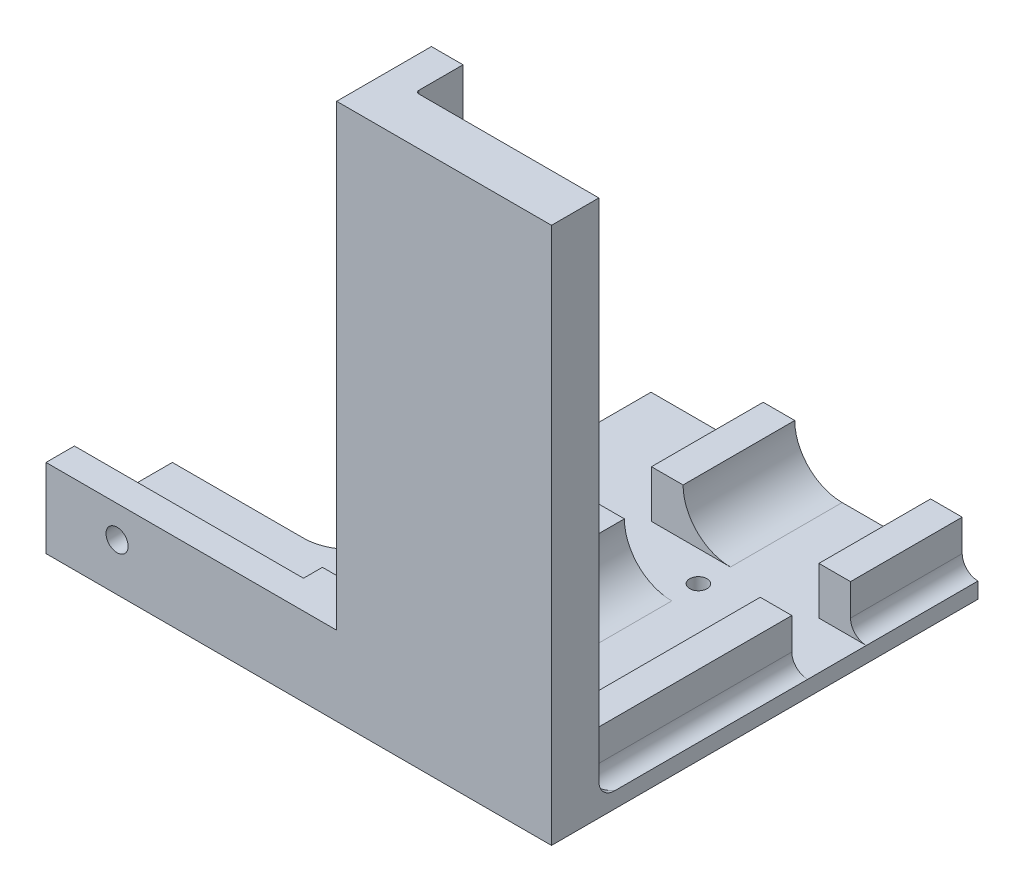
SolidWorks part; units mm, degrees
ref_plane "Front Plane" through (0, 0, 0) normal (0, 0, 1) x (1, 0, 0)
ref_plane "Top Plane" through (0, 0, 0) normal (0, 1, 0) x (1, 0, 0)
ref_plane "Right Plane" through (0, 0, 0) normal (1, 0, 0) x (0, 0, -1)
sketch "profile" plane through (0, 0, 0) normal (0, 0, 1) x (1, 0, 0)
  line L0 (11.8803, 7.4874) -> (14.5, 7.4874)
  line L1 (-5.5, 6.9749) -> (-7.8749, 4.6)
  line L2 (-7.8749, 4.6) -> (-12.1251, 4.6)
  line L3 (-12.1251, 4.6) -> (-14.5, 6.9749)
  line L4 (-8.1197, 7.4874) -> (-5.5, 7.4874)
  line L5 (-14.5, 6.9749) -> (-15.0126, 7.4874)
  line L6 (14.5, 6.9749) -> (12.1251, 4.6)
  line L7 (12.1251, 4.6) -> (7.8749, 4.6)
  line L8 (7.8749, 4.6) -> (5.5, 6.9749)
  line L9 (-14.7464, 10.3536) -> (-5.2536, 10.3536)
  line L10 (-14.5, 7.4874) -> (-11.8803, 7.4874)
  line L11 (5.5, 7.4874) -> (8.5334, 7.4874)
  line L12 (5.6673, 10.3536) -> (14.7464, 10.3536)
  line L13 (-15.0126, 7.4874) -> (-14.5, 7.4874)
  line L14 (-5.5, 6.9749) -> (-4.9874, 7.4874)
  line L15 (-4.9874, 7.4874) -> (-5.5, 7.4874)
  line L16 (5.5, 6.9749) -> (4.9874, 7.4874)
  line L17 (4.9874, 7.4874) -> (5.5, 7.4874)
  line L18 (14.5, 6.9749) -> (15.0126, 7.4874)
  line L19 (15.0126, 7.4874) -> (14.5, 7.4874)
  line L20 (-12.7464, 8.3536) -> (-14.7464, 10.3536)
  line L21 (-5.2536, 10.3536) -> (-7.2536, 8.3536)
  line L22 (7.6673, 8.3536) -> (5.6673, 10.3536)
  line L23 (14.7464, 10.3536) -> (12.7464, 8.3536)
  line L24 (-12.7464, 8.3536) -> (-11.8803, 7.4874)
  line L25 (-7.2536, 8.3536) -> (-8.1197, 7.4874)
  line L26 (7.6673, 8.3536) -> (8.5334, 7.4874)
  line L27 (12.7464, 8.3536) -> (11.8803, 7.4874)
  line L28 (-14.7464, 10.3536) -> (-20, 10.3536)
  line L29 (-20, 10.3536) -> (-20, 15.3536)
  line L30 (-20, 15.3536) -> (20, 15.3536)
  line L31 (20, 15.3536) -> (20, 10.3536)
  line L32 (20, 10.3536) -> (14.7464, 10.3536)
  line L33 (-5.2536, 10.3536) -> (5.6673, 10.3536)
  point P0 (-10, 4.6)
  point P1 (10, 4.6)
  dimension "D1" = 4.2503
  dimension "D2" = 5.7536
  dimension "D3" = 15.7497
  dimension "D4" = 20
  dimension "D5" = 5
extrude "Boss-Extrude1" add sketch "profile" along normal blind 250 contours L9 L33 L12 L32 L31 L30 L29 L28 region at (0, 12.8536, 0)
extrude "Boss-Extrude2" add sketch "Sketch1<3>" along normal blind 50 separate body contours L25 L21 L9 L20 L24 L10 L13 L5 L3 L2 L1 L14 L15 L4 | L27 L23 L12 L22 L26 L11 L17 L16 L8 L7 L6 L18 L19 L0 region at (10.0959, 7.5838, 0) region at (-10, 7.6238, 0)
sketch "Sketch1<3>" plane through (0, 0, 0) normal (0, 0, 1) x (1, 0, 0) same geometry as "profile"
pattern_linear "LPattern1" count 4 spacing 60 along (0, 0, 1) of "Boss-Extrude2"
sketch "Sketch2" plane through (0, 10.3536, 0) normal (0, -1, 0) x (1, 0, 0)
  line L0 (10, 250) -> (10, 0) construction
  line L1 (-20, 250) -> (20, 250) construction
  line L2 (12.1251, 0) -> (7.8749, 0) construction
  line L3 (-10, 230) -> (-10, 0) construction
  line L4 (-7.8749, 230) -> (-12.1251, 230) construction
  line L5 (-7.8749, 0) -> (-12.1251, 0) construction
  line L6 (-7.8749, 180) -> (-7.8749, 170) construction
  line L7 (-7.8749, 180) -> (-12.1251, 180) construction
  circle A0 centre (-10, 175) radius 2.75
  circle A1 centre (10, 175) radius 2.75
  circle A2 centre (-10, 115) radius 2.75
  circle A3 centre (10, 115) radius 2.75
  circle A4 centre (-10, 55) radius 2.75
  circle A5 centre (10, 55) radius 2.75
  point P21 (-7.8749, 175)
  dimension "D1" = 5.5
  dimension "D2" = 3
extrude "Cut-Extrude1" cut sketch "Sketch2" against normal through all
sketch "upper_acrylic_supp" plane through (0, 15.3536, 0) normal (0, 1, 0) x (1, 0, 0)
  line L0 (-20, 0) -> (20, 0) construction
  line L1 (-20, -250) -> (-34.5, -250) construction
  line L2 (-20, -250) -> (-20, 0) construction
  line L3 (-20, 0) -> (-34.5, 0) construction
  line L4 (-34.5, -250) -> (-34.5, 0) construction
  line L6 (-34.5, -250) -> (-24.5, -250)
  line L7 (-34.5, -250) -> (-34.5, -183.9264)
  line L8 (-34.5, -183.9264) -> (-24.5, -183.9264)
  line L9 (-24.5, -250) -> (-24.5, -183.9264)
  line L10 (-34.5, -165.3527) -> (-24.5, -165.3527)
  line L11 (-34.5, -165.3527) -> (-34.5, -123.8775)
  line L12 (-34.5, -123.8775) -> (-24.5, -123.8775)
  line L13 (-24.5, -165.3527) -> (-24.5, -123.8775)
  line L14 (-34.5, -106.5661) -> (-24.5, -106.5661)
  line L15 (-34.5, -106.5661) -> (-34.5, -64.0089)
  line L16 (-34.5, -64.0089) -> (-24.5, -64.0089)
  line L17 (-24.5, -106.5661) -> (-24.5, -64.0089)
  line L18 (-34.5, -45.5583) -> (-24.5, -45.5583)
  line L19 (-34.5, -45.5583) -> (-34.5, 0)
  line L20 (-34.5, 0) -> (-24.5, 0)
  line L21 (-24.5, -45.5583) -> (-24.5, 0)
  line L22 (-20, -250) -> (-40, -250)
  line L23 (-20, -250) -> (-20, 0)
  line L24 (-20, 0) -> (-40, 0)
  line L25 (-40, -250) -> (-40, 0)
  line M21 (-20, 0) -> (-20, -250)
  dimension "D1" = 5.5
  dimension "D2" = 10
  dimension "D3" = 20
extrude "Boss-Extrude3" add sketch "upper_acrylic_supp" against normal blind 5 contours L25 L22 L24 L21 L18 L19 L17 L14 L15 L16 L13 L10 L11 L12 L9 L6 L7 L8 M21 | L14 L17 L16 L15 | L10 L13 L12 L11 | L6 L9 L8 L7 | L18 L21 L20 L19 region at (-29.5, 15.3536, 216.9632) region at (-30.3215, 15.3536, 123.2164) region at (-29.5, 15.3536, 22.7792) region at (-29.5, 15.3536, 144.6151) region at (-29.5, 15.3536, 85.2875)
extrude "Boss-Extrude4" add sketch "upper_acrylic_supp<3>" along normal blind 15 contours L6 L9 L8 L7 | L10 L13 L12 L11 | L14 L17 L16 L15 | L18 L21 L20 L19 region at (-29.5, 15.3536, 216.9632) region at (-29.5, 15.3536, 22.7792) region at (-29.5, 15.3536, 144.6151) region at (-29.5, 15.3536, 85.2875)
sketch "upper_acrylic_supp<3>" plane through (0, 15.3536, 0) normal (0, 1, 0) x (1, 0, 0) same geometry as "upper_acrylic_supp"
fillet "Fillet1" radius 15 4 edges at (-24.5, 15.3536, 22.7792) (-24.5, 15.3536, 85.2875) (-24.5, 15.3536, 144.6151) (-24.5, 15.3536, 216.9632)
sketch "Sketch4" plane through (0, 15.3536, 0) normal (0, 1, 0) x (1, 0, 0)
  line L0 (20, -250) -> (20, 0) construction
  line L1 (-40, -250) -> (20, -250)
  line L2 (-40, -250) -> (-40, -265)
  line L3 (-40, -265) -> (20, -265)
  line L4 (20, -250) -> (20, -265)
  line L5 (-40, 0) -> (20, 0)
  line L6 (-40, 0) -> (-40, 15)
  line L7 (-40, 15) -> (20, 15)
  line L8 (20, 0) -> (20, 15)
  line L10 (-34.5, -265) -> (-34.5, 15) construction
  dimension "D1" = 15
  dimension "D2" = 15
extrude "Boss-Extrude5" add sketch "Sketch4" along normal mid plane 10
extrude "Boss-Extrude6" add sketch "Sketch4<3>" along normal blind 60
sketch "Sketch4<3>" plane through (0, 15.3536, 0) normal (0, 1, 0) x (1, 0, 0) same geometry as "Sketch4"
sketch "Sketch5" plane through (0, 0, 250) normal (0, 0, -1) x (-1, 0, 0)
  line L0 (-20, 75.3536) -> (40, 75.3536) construction
  line L1 (40, 15.3536) -> (34.5, 15.3536)
  line L2 (40, 15.3536) -> (40, 75.3536)
  line L3 (40, 75.3536) -> (34.5, 75.3536)
  line L4 (34.5, 15.3536) -> (34.5, 75.3536)
  line L6 (34.5, 15.3536) -> (24.5, 15.3536)
  line L7 (34.5, 15.3536) -> (34.5, 75.3536)
  line L8 (34.5, 75.3536) -> (24.5, 75.3536)
  line L9 (24.5, 15.3536) -> (24.5, 75.3536)
  line M5 (40, 75.3536) -> (-20, 75.3536)
  line M9 (24.5, 30.3536) -> (34.5, 30.3536)
  dimension "D1" = 5.5
  dimension "D2" = 10
extrude "Boss-Extrude7" add sketch "Sketch5" along normal blind 15 contours L9 L4 M9 M5 region at (-29.5, 52.8536, 250)
extrude "Boss-Extrude8" add sketch "Sketch5<3>" against normal blind 15 from surface contours L9 L4 M9 M5 region at (-29.5, 52.8536, 250) starting at face at (-18.2633, 33.7152, 0)
sketch "Sketch5<3>" plane through (0, 0, 250) normal (0, 0, -1) x (-1, 0, 0) same geometry as "Sketch5"
fillet "Fillet2" radius 1 6 edges at (5.25, 15.3536, 0) (-20.1066, 19.747, 0) (5.25, 15.3536, 250) (-20.1066, 19.747, 250) (-24.5, 52.8536, 0) (-24.5, 52.8536, 250)
sketch "Sketch6" plane through (-40, 0, 0) normal (-1, 0, 0) x (0, 0, 1)
  line L1 (250, 15.3536) -> (256, 15.3536)
  line L2 (250, 15.3536) -> (250, 75.3536)
  line L3 (250, 75.3536) -> (256, 75.3536)
  line L4 (256, 15.3536) -> (256, 75.3536)
  line L6 (0, 15.3536) -> (-6, 15.3536)
  line L7 (0, 15.3536) -> (0, 75.3536)
  line L8 (0, 75.3536) -> (-6, 75.3536)
  line L9 (-6, 15.3536) -> (-6, 75.3536)
  dimension "D1" = 6
  dimension "D2" = 6
extrude "Cut-Extrude2" cut sketch "Sketch6" against normal blind 6
sketch "Sketch7" plane through (-40, 0, 0) normal (-1, 0, 0) x (0, 0, 1)
  line L8 (265, 75.3536) -> (256, 75.3536)
  line L9 (256, 75.3536) -> (256, 15.3536)
  line L10 (256, 15.3536) -> (-6, 15.3536)
  line L11 (-6, 15.3536) -> (-6, 75.3536)
  line L12 (-6, 75.3536) -> (-15, 75.3536)
  line L13 (-15, 75.3536) -> (-15, 10.3536)
  line L14 (-15, 10.3536) -> (265, 10.3536)
  line L15 (265, 10.3536) -> (265, 75.3536)
  line L16 (265, 75.3536) -> (256, 75.3536)
  line L17 (256, 75.3536) -> (256, 15.3536)
  line L18 (256, 15.3536) -> (-6, 15.3536)
  line L19 (-6, 15.3536) -> (-6, 75.3536)
  line L20 (-6, 75.3536) -> (-15, 75.3536)
  line L21 (-15, 75.3536) -> (-15, 10.3536)
  line L22 (-15, 10.3536) -> (265, 10.3536)
  line L23 (265, 10.3536) -> (265, 75.3536)
  dimension "D1" = 0
extrude "Boss-Extrude9" add sketch "Sketch7" along normal blind 30
sketch "Sketch8" plane through (-70, 0, 0) normal (-1, 0, 0) x (0, 0, 1)
  line L0 (-15, 10.3536) -> (265, 10.3536) construction
  line L1 (-44.3745, 35.3536) -> (289.2282, 35.3536)
  line L2 (-44.3745, 35.3536) -> (-44.3745, 94.3849)
  line L3 (-44.3745, 94.3849) -> (289.2282, 94.3849)
  line L4 (289.2282, 35.3536) -> (289.2282, 94.3849)
  dimension "D1" = 25
extrude "Cut-Extrude3" cut sketch "Sketch8" against normal blind 150
sketch "Sketch9" plane through (-34, 0, 0) normal (-1, 0, 0) x (0, 0, 1)
  line L4 (256, 15.3536) -> (256, 35.3536)
  line L5 (256, 35.3536) -> (250, 35.3536)
  line L6 (250, 35.3536) -> (250, 15.3536)
  line L7 (250, 15.3536) -> (256, 15.3536)
  line L8 (256, 15.3536) -> (256, 35.3536)
  line L9 (256, 35.3536) -> (250, 35.3536)
  line L10 (250, 35.3536) -> (250, 15.3536)
  line L11 (250, 15.3536) -> (256, 15.3536)
  line L12 (0, 35.3536) -> (-6, 35.3536)
  line L13 (-6, 35.3536) -> (-6, 15.3536)
  line L14 (-6, 15.3536) -> (0, 15.3536)
  line L15 (0, 15.3536) -> (0, 35.3536)
  line L16 (0, 35.3536) -> (-6, 35.3536)
  line L17 (-6, 35.3536) -> (-6, 15.3536)
  line L18 (-6, 15.3536) -> (0, 15.3536)
  line L19 (0, 15.3536) -> (0, 35.3536)
  dimension "D1" = 0
  dimension "D2" = 0
extrude "cloth_escape_gap" add sketch "Sketch9" along normal blind 20
sketch "Sketch11" plane through (-70, 0, 0) normal (-1, 0, 0) x (0, 0, 1)
  line L0 (256, 35.3536) -> (256, 15.3536) construction
  line L1 (-15, 35.3536) -> (-6, 35.3536)
  line L2 (-15, 35.3536) -> (-15, 15.3536)
  line L3 (-15, 15.3536) -> (-6, 15.3536)
  line L4 (-6, 35.3536) -> (-6, 15.3536)
  line L5 (265, 35.3536) -> (256, 35.3536)
  line L6 (265, 35.3536) -> (265, 15.3536)
  line L7 (265, 15.3536) -> (256, 15.3536)
  line L8 (256, 35.3536) -> (256, 15.3536)
  line L9 (256, 15.3536) -> (256, 35.3536) construction
extrude "Boss-Extrude11" add sketch "Sketch11" along normal blind 100
sketch "Sketch12" plane through (0, 10.3536, 0) normal (0, -1, 0) x (1, 0, 0)
  line L0 (-70, -15) -> (-170, -10.5)
  line L1 (-170, -15) -> (-170, -6) construction
  line L2 (-170, -10.5) -> (-170, -15)
  line L3 (-170, -15) -> (-70, -15) construction
  line L4 (-170, -15) -> (-70, -15)
  line L5 (-70, 265) -> (-170, 260.5)
  line L6 (-170, 256) -> (-170, 265) construction
  line L7 (-170, 260.5) -> (-170, 265)
  line L8 (-170, 265) -> (-70, 265)
extrude "Cut-Extrude4" cut sketch "Sketch12" against normal blind 68 contours L8 L7 L5 | L0 L2 L4 region at (-136.6667, 10.3536, 263.5)
sketch "Sketch13" plane through (-70, 0, 0) normal (-1, 0, 0) x (0, 0, 1)
  line L0 (256, 15.3536) -> (265, 15.3536) construction
  line L1 (-15, 10.3536) -> (25, 10.3536)
  line L2 (-15, 10.3536) -> (-15, 15.3536)
  line L3 (-15, 15.3536) -> (25, 15.3536)
  line L4 (25, 10.3536) -> (25, 15.3536)
  line L5 (265, 10.3536) -> (225, 10.3536)
  line L6 (265, 10.3536) -> (265, 15.3536)
  line L7 (265, 15.3536) -> (225, 15.3536)
  line L8 (225, 10.3536) -> (225, 15.3536)
  line L9 (256, 15.3536) -> (-6, 15.3536) construction
  dimension "D1" = 40
  dimension "D2" = 40
extrude "Boss-Extrude13" add sketch "Sketch13" along normal blind 100
sketch "Sketch14" plane through (0, 15.3536, 0) normal (0, 1, 0) x (1, 0, 0)
  line L3 (-70, -265) -> (-170, -260.5)
  line L4 (-170, -260.5) -> (-170, -265)
  line L5 (-170, -265) -> (-70, -265)
  line L6 (-70, -265) -> (-170, -260.5)
  line L7 (-170, -260.5) -> (-170, -265)
  line L8 (-170, -265) -> (-70, -265)
  line L9 (-170, 15) -> (-170, 10.5)
  line L10 (-170, 10.5) -> (-70, 15)
  line L11 (-70, 15) -> (-170, 15)
  line L12 (-170, 15) -> (-170, 10.5)
  line L13 (-170, 10.5) -> (-70, 15)
  line L14 (-70, 15) -> (-170, 15)
  dimension "D1" = 0
  dimension "D2" = 0
extrude "Cut-Extrude5" cut sketch "Sketch14" against normal blind 100
fillet "Fillet3" radius 15 2 edges at (-70, 12.8536, 25) (-70, 12.8536, 225)
sketch "Sketch16" plane through (0, 15.3536, 0) normal (0, 1, 0) x (1, 0, 0)
  line L0 (20, -1) -> (-9.5, -1) construction
  line L1 (-34.5, -235) -> (18.5, -235) construction
  line L2 (-34.5, -235) -> (-34.5, -1) construction
  line L3 (-34.5, -1) -> (18.5, -1) construction
  line L4 (18.5, -235) -> (18.5, -1) construction
  line L5 (20, -265) -> (-70, -265) construction
  line L6 (18.5, -265) -> (33.5, -265)
  line L7 (18.5, -265) -> (18.5, 15)
  line L8 (18.5, 15) -> (33.5, 15)
  line L9 (33.5, -265) -> (33.5, 15)
  line L10 (-70, 15) -> (20, 15) construction
  line L11 (18.5, -250) -> (33.5, -250)
  line L12 (18.5, 0) -> (33.5, 0)
  line L13 (-23.5, -250) -> (20, -250) construction
  line L14 (-9.5, 0) -> (20, 0) construction
  line L15 (18.5, -250) -> (28.5, -250)
  line L16 (28.5, -250) -> (28.5, -183.9264)
  line L17 (28.5, 0) -> (18.5, 0)
  line L18 (18.5, -183.9264) -> (28.5, -183.9264)
  line L19 (18.5, -165.3527) -> (28.5, -165.3527)
  line L20 (18.5, -123.8775) -> (28.5, -123.8775)
  line L21 (18.5, -106.5661) -> (28.5, -106.5661)
  line L22 (18.5, -64.0089) -> (28.5, -64.0089)
  line L23 (18.5, -43.1778) -> (28.5, -43.1778)
  line L24 (-34.5, -165.3527) -> (-9.5, -165.3527) construction
  line L25 (-34.5, -183.9264) -> (-9.5, -183.9264) construction
  line L26 (-34.5, -106.5661) -> (-9.5, -106.5661) construction
  line L27 (-34.5, -123.8775) -> (-9.5, -123.8775) construction
  line L28 (-9.5, -64.0089) -> (-24.5, -64.0089) construction
  line L30 (28.5, -165.3527) -> (28.5, -123.8775)
  line L31 (28.5, -106.5661) -> (28.5, -64.0089)
  line L32 (28.5, -43.1778) -> (28.5, 0)
  line M38 (-9.5, -249) -> (20, -249)
  line M39 (20, -249) -> (20, -1)
  line M40 (20, -1) -> (-9.5, -1)
  dimension "D1" = 53
  dimension "D2" = 15
  dimension "D3" = 10
extrude "Boss-Extrude14" add sketch "Sketch16" along direction (0, -1, 0) on the side of the normal up to surface (20 mm away) from surface contours L7 L12 L9 L8 | L11 L7 L6 L9 region at (26, 15.3536, 257.5) region at (26, 15.3536, -7.5) up to face at (-51.6423, 35.3536, 251.8089) starting at face at (-10, 10.3536, 25)
extrude "Cut-Extrude6" cut sketch "Sketch16<5>" against normal blind 10 and the other way blind 30 contours L11 L7 L6 L9 | L32 L23 L22 L31 L21 L20 L30 L19 L18 L16 L11 L9 L12 M39 | L19 L30 L20 M39 | L21 L31 L22 M39 | L23 L32 L12 L7 M40 M39 | L7 L12 L9 L8 | L7 L23 M39 M40 | L23 L7 L22 M39 | L22 L7 L21 M39 | L21 L7 L20 M39 | L20 L7 L19 M39 | L19 L7 L18 M39 | L18 L7 M38 M39 | L18 L7 L11 L16 M39 M38 region at (26, 15.3536, 257.5) region at (24.2367, 15.3536, 217.0499) region at (29.1213, 15.3536, 121.3942) region at (19.25, 15.3536, 216.4632) region at (26, 15.3536, -7.5) region at (19.25, 15.3536, 174.6396) region at (24.2296, 15.3536, 21.5031) region at (19.25, 15.3536, 144.6151) region at (19.25, 15.3536, 115.2218) region at (24.25, 15.3536, 144.6151) region at (19.25, 15.3536, 22.0889) region at (19.25, 15.3536, 53.5934) region at (19.25, 15.3536, 85.2875) region at (24.25, 15.3536, 85.2875)
sketch "Sketch16<5>" plane through (0, 15.3536, 0) normal (0, 1, 0) x (1, 0, 0) same geometry as "Sketch16"
extrude "Boss-Extrude15" add sketch "Sketch16<6>" against normal up to surface (5 mm away) contours L32 L23 L22 L31 L21 L20 L30 L19 L18 L16 L11 L9 L12 M39 | L18 L7 L11 L16 M39 M38 | L11 L7 L6 L9 | L19 L30 L20 M39 | L21 L31 L22 M39 | L23 L32 L12 L7 M40 M39 | L7 L12 L9 L8 | L7 L23 M39 M40 | L23 L7 L22 M39 | L22 L7 L21 M39 | L21 L7 L20 M39 | L20 L7 L19 M39 | L19 L7 L18 M39 | L18 L7 M38 M39 region at (26, 15.3536, 257.5) region at (24.2367, 15.3536, 217.0499) region at (29.1213, 15.3536, 121.3942) region at (19.25, 15.3536, 216.4632) region at (26, 15.3536, -7.5) region at (19.25, 15.3536, 174.6396) region at (24.2296, 15.3536, 21.5031) region at (19.25, 15.3536, 144.6151) region at (19.25, 15.3536, 115.2218) region at (24.25, 15.3536, 144.6151) region at (19.25, 15.3536, 22.0889) region at (19.25, 15.3536, 53.5934) region at (19.25, 15.3536, 85.2875) region at (24.25, 15.3536, 85.2875) up to face at (-90.5656, 10.3536, 125)
sketch "Sketch16<6>" plane through (0, 15.3536, 0) normal (0, 1, 0) x (1, 0, 0) same geometry as "Sketch16"
extrude "Boss-Extrude16" add sketch "Sketch16<7>" along normal up to surface (20 mm away) contours L11 L7 L6 L9 | L7 L12 L9 L8 region at (26, 15.3536, 257.5) region at (26, 15.3536, -7.5) up to face at (-51.8923, 35.3536, 251.8089)
sketch "Sketch16<7>" plane through (0, 15.3536, 0) normal (0, 1, 0) x (1, 0, 0) same geometry as "Sketch16"
extrude "Boss-Extrude17" add sketch "Sketch16<8>" along normal up to surface (15 mm away) contours L18 L7 L11 L16 M39 M38 | L19 L30 L20 M39 | L21 L31 L22 M39 | L23 L32 L12 L7 M40 M39 | L7 L23 M39 M40 | L22 L7 L21 M39 | L20 L7 L19 M39 | L18 L7 M38 M39 region at (24.2367, 15.3536, 217.0499) region at (19.25, 15.3536, 216.4632) region at (24.2296, 15.3536, 21.5031) region at (19.25, 15.3536, 144.6151) region at (24.25, 15.3536, 144.6151) region at (19.25, 15.3536, 22.0889) region at (19.25, 15.3536, 85.2875) region at (24.25, 15.3536, 85.2875) up to face at (-29.5, 30.3536, 209.4632)
sketch "Sketch16<8>" plane through (0, 15.3536, 0) normal (0, 1, 0) x (1, 0, 0) same geometry as "Sketch16"
extrude "Boss-Extrude18" add sketch "Sketch14<2>" along normal up to surface (20 mm away) and the other way up to surface (5 mm away) up to face at (-49.3923, 35.3536, -1.8089) other way up to face at (-88.0656, 10.3536, 125)
sketch "Sketch14<2>" plane through (0, 15.3536, 0) normal (0, 1, 0) x (1, 0, 0) same geometry as "Sketch14"
fillet "Fillet4" radius 5 6 edges at (31, 15.3536, 250) (31, 15.3536, 0) (28.5, 15.3536, 21.5889) (28.5, 15.3536, 85.2875) (28.5, 15.3536, 144.6151) (28.5, 15.3536, 216.9632)
sketch "Sketch18" plane through (0, 35.3536, 0) normal (0, 1, 0) x (1, 0, 0)
  line L2 (-34.5, -250) -> (-34.5, -265)
  line L3 (-34.5, 15) -> (-34.5, 0)
  line L12 (-23.5, 0) -> (33.5, 0)
  line L13 (33.5, 0) -> (33.5, 15)
  line L14 (33.5, 15) -> (-170, 15)
  line L15 (-170, 15) -> (-170, 6)
  line L30 (-170, 6) -> (-54, 6)
  line L32 (-54, 6) -> (-54, 0)
  line L38 (-54, 0) -> (-34.5, 0)
  line L39 (-34.5, 0) -> (-34.5, -15)
  line L50 (-34.5, -15) -> (-24.5, -15)
  line L51 (-24.5, -15) -> (-24.5, -1)
  line L52 (-23.5, 0) -> (33.5, 0)
  line L53 (33.5, 0) -> (33.5, 15)
  line L54 (33.5, 15) -> (-34.5, 15)
  line L59 (-34.5, 0) -> (-34.5, -15)
  line L60 (-34.5, -15) -> (-24.5, -15)
  line L61 (-24.5, -15) -> (-24.5, -1)
  line L62 (-170, -265) -> (33.5, -265)
  line L63 (33.5, -265) -> (33.5, -250)
  line L64 (33.5, -250) -> (-23.5, -250)
  line L65 (-24.5, -249) -> (-24.5, -235)
  line L66 (-24.5, -235) -> (-34.5, -235)
  line L67 (-34.5, -235) -> (-34.5, -250)
  line L68 (-34.5, -250) -> (-54, -250)
  line L69 (-54, -250) -> (-54, -256)
  line L70 (-54, -256) -> (-170, -256)
  line L71 (-170, -256) -> (-170, -265)
  line L72 (-34.5, -265) -> (33.5, -265)
  line L73 (33.5, -265) -> (33.5, -250)
  line L74 (33.5, -250) -> (-23.5, -250)
  line L75 (-24.5, -249) -> (-24.5, -235)
  line L76 (-24.5, -235) -> (-34.5, -235)
  line L77 (-34.5, -235) -> (-34.5, -250)
  arc A5 (-23.5, 0) -> (-24.5, -1) centre (-23.5, -1) ccw
  arc A6 (-23.5, 0) -> (-24.5, -1) centre (-23.5, -1) ccw
  arc A7 (-24.5, -249) -> (-23.5, -250) centre (-23.5, -249) ccw
  arc A8 (-24.5, -249) -> (-23.5, -250) centre (-23.5, -249) ccw
  dimension "D1" = 0
  dimension "D2" = 0
extrude "Boss-Extrude21" add sketch "Sketch18" along normal blind 170 from surface starting at face at (-91.6787, 10.3536, 125)
sketch "Sketch19" plane through (0, 15.3536, 0) normal (0, 1, 0) x (1, 0, 0)
  line L0 (-170, -25) -> (-170, 6) construction
  line L1 (-70, -125) -> (-196.5165, -125) construction
  line L2 (-70, -210) -> (-70, -40) construction
  circle A0 centre (-154, -9.5) radius 3.5
  circle A1 centre (-104, -9.5) radius 3.5
  circle A2 centre (-104, -240.5) radius 3.5
  circle A3 centre (-154, -240.5) radius 3.5
  point P6 (-170, -9.5)
  dimension "D1" = 7
  dimension "D2" = 50
  dimension "D3" = 50
extrude "Cut-Extrude7" cut sketch "Sketch19" against normal blind 10
sketch "Sketch20" plane through (0, 0, 256) normal (0, 0, -1) x (-1, 0, 0)
  line L4 (34.5, 35.3536) -> (34.5, 15.3536)
  line L5 (34.5, 15.3536) -> (54, 15.3536)
  line L6 (54, 15.3536) -> (54, 35.3536)
  line L7 (54, 35.3536) -> (34.5, 35.3536)
  line L8 (34.5, 35.3536) -> (34.5, 15.3536)
  line L9 (34.5, 15.3536) -> (54, 15.3536)
  line L10 (54, 15.3536) -> (54, 35.3536)
  line L11 (54, 35.3536) -> (34.5, 35.3536)
  circle A0 centre (104, 25.3536) radius 3.5
  circle A1 centre (154, 25.3536) radius 3.5
  point P8 (54, 25.3536)
  dimension "D3" = 7
  dimension "D2" = 50
  dimension "D4" = 50
  dimension "D1" = 0
extrude "Cut-Extrude8" cut sketch "Sketch20" against normal blind 10 and the other way blind 355 contours A0 | A1 region at (-104, 25.3536, 256) region at (-154, 25.3536, 256)
sketch "Sketch21" plane through (0, 0, 0) normal (0, 0, 1) x (1, 0, 0)
  line L1 (13.5, 15.3536) -> (-1.5, 15.3536)
  line L2 (13.5, 15.3536) -> (13.5, 212.8546)
  line L3 (13.5, 212.8546) -> (-1.5, 212.8546)
  line L4 (-1.5, 15.3536) -> (-1.5, 212.8546)
  line L6 (18.5, 15.3536) -> (-9.5, 15.3536) construction
  line L7 (18.5, 30.3536) -> (18.5, 16.3536) construction
  dimension "D1" = 15
  dimension "D2" = 5
extrude "Cut-Extrude9" cut sketch "Sketch21" against normal blind 130
sketch "Sketch22" plane through (0, 0, 0) normal (0, 1, 0) x (1, 0, 0)
  line L5 (33.5, 15) -> (-126.5, 15)
  line L6 (33.5, 15) -> (33.5, -120)
  line L7 (33.5, -120) -> (-126.5, -120)
  line L8 (-126.5, 15) -> (-126.5, -120)
  line L11 (33.5, -265) -> (-126.5, -265)
  line L12 (33.5, -265) -> (33.5, -130)
  line L13 (33.5, -130) -> (-126.5, -130)
  line L14 (-126.5, -265) -> (-126.5, -130)
  line L15 (-126.5, -120) -> (-126.5, -130)
  line L16 (33.5, -120) -> (33.5, -130)
  line L19 (-126.5, 15) -> (-186.5, 15)
  line L20 (-126.5, 15) -> (-126.5, -265)
  line L21 (-126.5, -265) -> (-186.5, -265)
  line L22 (-186.5, 15) -> (-186.5, -265)
  dimension "D1" = 160
  dimension "D2" = 135
  dimension "D3" = 135
  dimension "D4" = 60
extrude "Cut-Extrude11" cut sketch "Sketch22" along normal blind 270 contours L5 L8 L7 L6 | L16 L7 L15 L13 | L19 L22 L21 L14 L15 L8 region at (-46.5, 0, 52.5) region at (-156.5, 0, 125) region at (-46.5, 0, 125)
